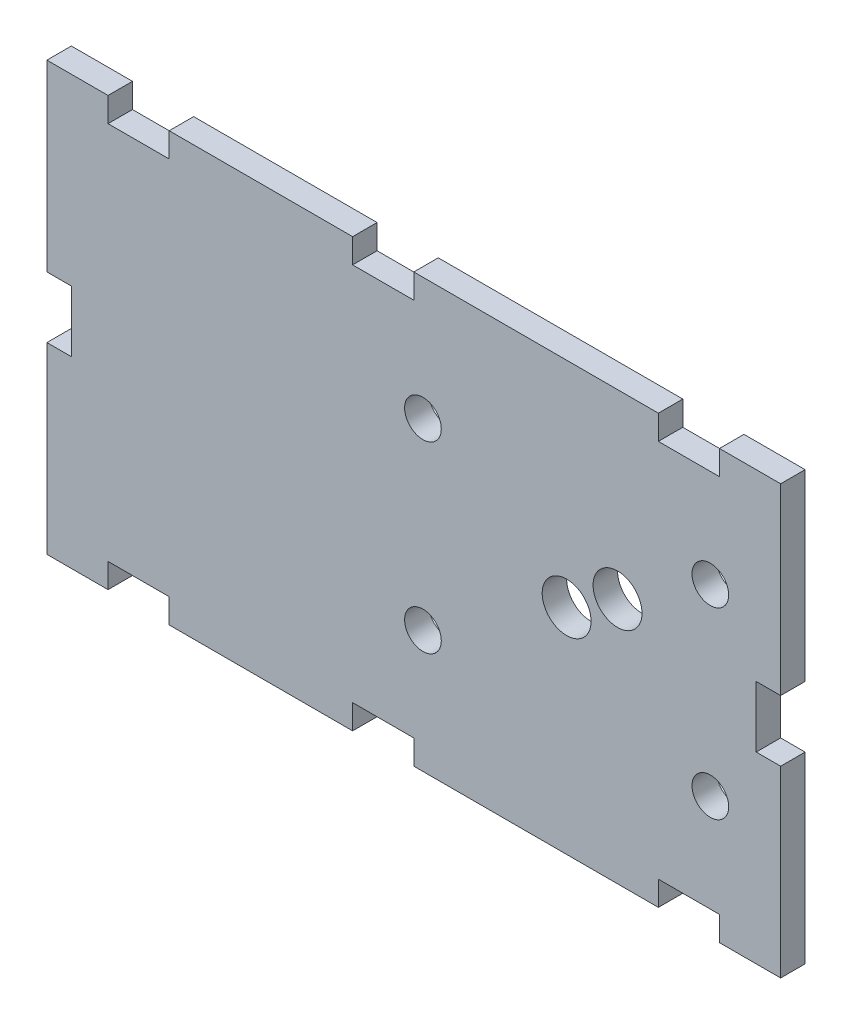
SolidWorks part; units mm, degrees
ref_plane "Front Plane" through (0, 0, 0) normal (0, 0, 1) x (1, 0, 0)
ref_plane "Top Plane" through (0, 0, 0) normal (0, 1, 0) x (1, 0, 0)
ref_plane "Right Plane" through (0, 0, 0) normal (1, 0, 0) x (0, 0, -1)
sketch "Sketch1" plane through (0, 0, 0) normal (0, 0, 1) x (1, 0, 0)
  line L1 (0, 0) -> (120, 0)
  line L2 (0, 0) -> (0, 70)
  line L3 (0, 70) -> (120, 70)
  line L4 (120, 0) -> (120, 70)
  dimension "D1" = 120
  dimension "D2" = 70
extrude "Boss-Extrude1" add sketch "Sketch1" along normal blind 4
sketch "Sketch2" plane through (0, 0, 4) normal (0, 0, 1) x (1, 0, 0)
  line L0 (120, 35) -> (27.3508, 35) construction
  line L1 (120, 0) -> (120, 70) construction
  line L3 (61.5, 20) -> (108.5, 20) construction
  line L4 (61.5, 20) -> (61.5, 50) construction
  line L5 (61.5, 50) -> (108.5, 50) construction
  line L6 (108.5, 20) -> (108.5, 50) construction
  line L7 (61.5, 20) -> (108.5, 50) construction
  line L8 (61.5, 50) -> (108.5, 20) construction
  circle A0 centre (85, 35) radius 4
  circle A1 centre (108.5, 50) radius 3
  circle A2 centre (108.5, 20) radius 3
  circle A3 centre (61.5, 20) radius 3
  circle A4 centre (61.5, 50) radius 3
  dimension "D1" = 8
  dimension "D2" = 35
  dimension "D5" = 6
  dimension "D3" = 47
  dimension "D4" = 30
extrude "Cut-Extrude1" cut sketch "Sketch2" against normal blind 4
sketch "Sketch3" plane through (0, 0, 4) normal (0, 0, 1) x (1, 0, 0)
  line L0 (85, 35) -> (108.5, 50) construction
  circle A0 centre (93.3228, 40.3124) radius 4
  point P6 (0, 0)
  dimension "D1" = 8
extrude "Cut-Extrude2" cut sketch "Sketch3" against normal blind 4
sketch "Sketch4" plane through (0, 0, 4) normal (0, 0, 1) x (1, 0, 0)
  line L0 (0, 0) -> (120, 0) construction
  line L1 (10, 0) -> (20, 0)
  line L2 (10, 0) -> (10, 4)
  line L3 (10, 4) -> (20, 4)
  line L4 (20, 0) -> (20, 4)
  line L5 (120, 0) -> (120, 70) construction
  line L6 (50, 0) -> (60, 0)
  line L7 (50, 0) -> (50, 4)
  line L8 (50, 4) -> (60, 4)
  line L9 (60, 0) -> (60, 4)
  line L10 (100, 0) -> (110, 0)
  line L11 (100, 0) -> (100, 4)
  line L12 (100, 4) -> (110, 4)
  line L13 (110, 0) -> (110, 4)
  line L14 (0, 70) -> (0, 0) construction
  line L15 (120, 70) -> (0, 70) construction
  line L16 (0, 40) -> (4, 40)
  line L17 (0, 40) -> (0, 30)
  line L18 (0, 30) -> (4, 30)
  line L19 (4, 40) -> (4, 30)
  line L20 (120, 40) -> (116, 40)
  line L21 (120, 40) -> (120, 30)
  line L22 (120, 30) -> (116, 30)
  line L23 (116, 40) -> (116, 30)
  line L25 (120, 40) -> (116, 40)
  line L26 (120, 30) -> (116, 30)
  line L27 (0, 40) -> (4, 40)
  line L28 (0, 30) -> (4, 30)
  line L29 (110, 70) -> (110, 66)
  line L30 (100, 66) -> (110, 66)
  line L31 (100, 70) -> (100, 66)
  line L32 (100, 70) -> (110, 70)
  line L33 (60, 70) -> (60, 66)
  line L34 (50, 66) -> (60, 66)
  line L35 (50, 70) -> (50, 66)
  line L36 (50, 70) -> (60, 70)
  line L37 (20, 70) -> (20, 66)
  line L38 (10, 66) -> (20, 66)
  line L39 (10, 70) -> (10, 66)
  line L40 (10, 70) -> (20, 70)
  line M22 (0, 70) -> (0, 0)
  line M23 (0, 0) -> (120, 0)
  line M24 (120, 0) -> (120, 70)
  line M25 (120, 70) -> (0, 70)
  dimension "D1" = 10
  dimension "D2" = 4
  dimension "D3" = 10
  dimension "D4" = 10
  dimension "D5" = 30
  dimension "D6" = 30
  dimension "D7" = 30
extrude "Cut-Extrude3" cut sketch "Sketch4" against normal blind 4 contours L39 L38 L37 M25 | L31 L30 L29 M25 | L20 L23 L22 M24 | L13 L12 L11 M23 | L9 L8 L7 M23 | L4 L3 L2 M23 | L19 L16 L18 M22 | L36 L33 L34 L35 region at (15, 2, 4) region at (55, 2, 4) region at (2, 35, 4) region at (105, 2, 4) region at (15, 68, 4) region at (118, 35, 4) region at (105, 68, 4)
